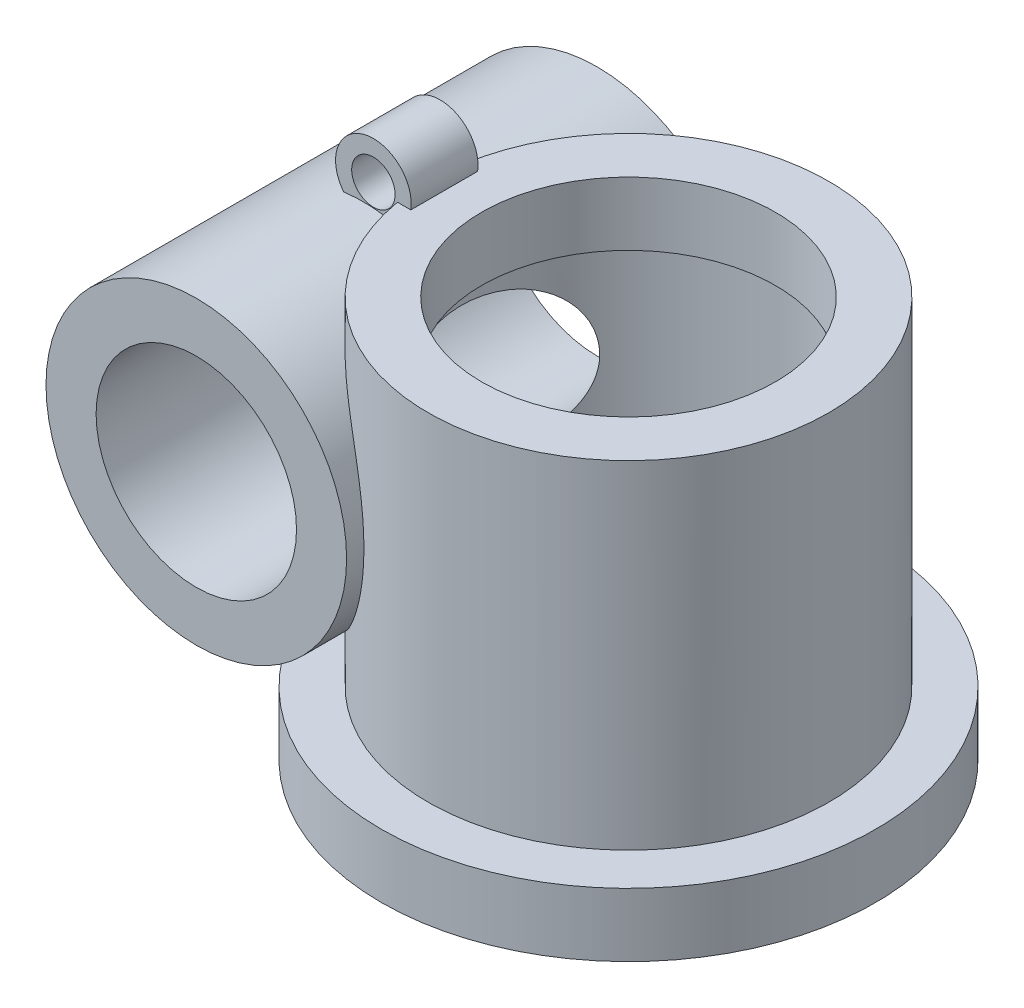
SolidWorks part; units mm, degrees
ref_plane "Front Plane" through (0, 0, 0) normal (0, 0, 1) x (1, 0, 0)
ref_plane "Top Plane" through (0, 0, 0) normal (0, 1, 0) x (1, 0, 0)
ref_plane "Right Plane" through (0, 0, 0) normal (1, 0, 0) x (0, 0, -1)
sketch "Sketch1" plane through (0, 0, 0) normal (0, 1, 0) x (1, 0, 0)
  circle A0 centre (0, 0) radius 3
  circle A1 centre (0, 0) radius 2.5
  dimension "D1" = 6
  dimension "D2" = 5
extrude "Boss-Extrude1" add sketch "Sketch1" along normal blind 5 and the other way blind 1
sketch "Sketch2" plane through (0, 0, 0) normal (0, 0, 1) x (1, 0, 0)
  circle A0 centre (-3.47, 2.5) radius 2.25
  circle A1 centre (-3.47, 2.5) radius 1.5
  dimension "D1" = 4.5
  dimension "D3" = 3
  dimension "D2" = 3.47
extrude "Boss-Extrude2" add sketch "Sketch2" along normal blind 3 and the other way blind 3
sketch "Sketch3" plane through (0, 0, 3) normal (0, 0, 1) x (1, 0, 0)
  circle A0 centre (-3.47, 2.5) radius 1.5 construction
  circle A1 centre (-3.47, 2.5) radius 1.5
extrude "Cut-Extrude1" cut sketch "Sketch3" against normal through all
sketch "Sketch4" plane through (0, 5, 0) normal (0, 1, 0) x (1, 0, 0)
  circle A0 centre (0, 0) radius 2.5 construction
  circle A1 centre (0, 0) radius 2.5
extrude "Cut-Extrude2" cut sketch "Sketch4" against normal through all
sketch "Sketch5" plane through (0, 0, 0) normal (0, 0, 1) x (1, 0, 0)
  circle A0 centre (-3.319, 5.0802) radius 0.5661
  circle A1 centre (-3.319, 5.0802) radius 0.3249
extrude "Boss-Extrude3" add sketch "Sketch5" along normal blind 0.5 and the other way blind 0.5
sketch "Sketch6" plane through (0, -1, 0) normal (0, -1, 0) x (1, 0, 0)
  circle A0 centre (0, 0) radius 3 construction
  circle A1 centre (0, 0) radius 3
  circle A2 centre (0, 0) radius 3.7
  dimension "D1" = 0.7
extrude "Boss-Extrude4" add sketch "Sketch6" against normal blind 0.95
sketch "Sketch7" plane through (0, 5, 0) normal (0, 1, 0) x (1, 0, 0)
  circle A0 centre (0, 0) radius 2.5 construction
  circle A1 centre (0, 0) radius 2.5
  circle A2 centre (0, 0) radius 2.2
  dimension "D1" = 0.3
extrude "Boss-Extrude5" add sketch "Sketch7" against normal blind 0.95
